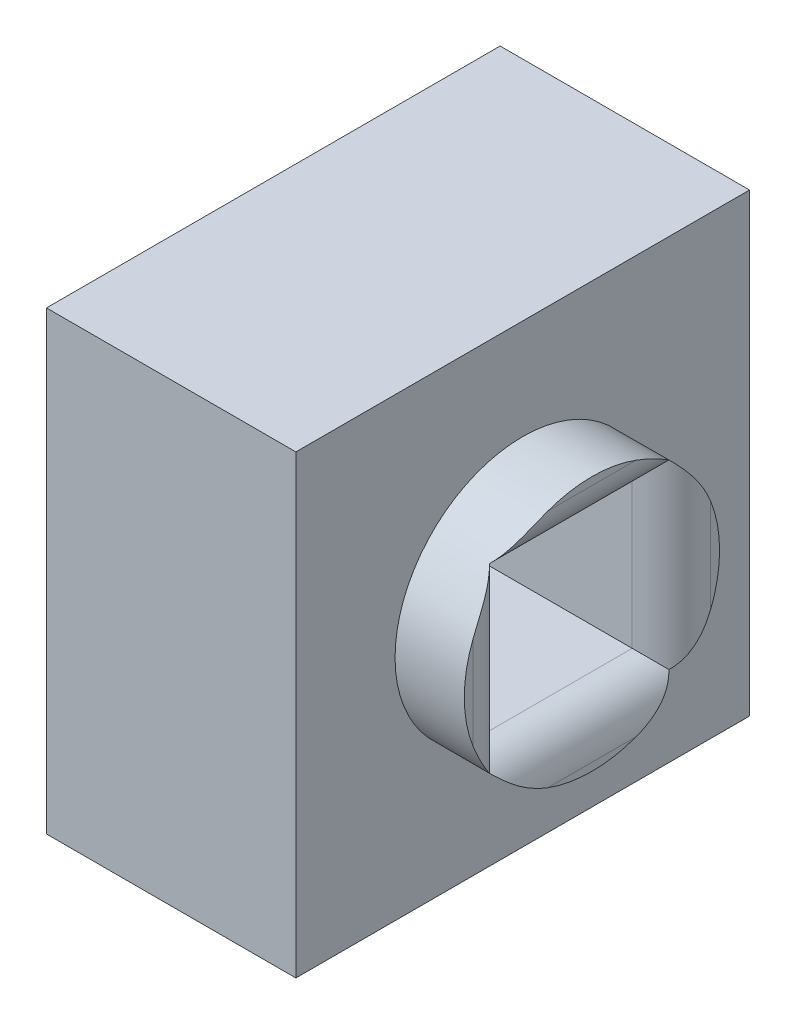
SolidWorks part; units mm, degrees
ref_plane "Front" through (0, 0, 0) normal (0, 0, 1) x (1, 0, 0)
ref_plane "Top" through (0, 0, 0) normal (0, 1, 0) x (1, 0, 0)
ref_plane "Right" through (0, 0, 0) normal (1, 0, 0) x (0, 0, -1)
sketch "Sketch2" plane through (0, 0, 0) normal (1, 0, 0) x (0, 0, -1)
  line L1 (0, 0) -> (8.1, 0)
  line L2 (0, 0) -> (0, 8.2)
  line L3 (0, 8.2) -> (8.1, 8.2)
  line L4 (8.1, 0) -> (8.1, 8.2)
  dimension "D1" = 8.2
  dimension "D2" = 8.1
extrude "Extrude-Thin1" add sketch "Sketch2" along normal blind 12.7 thin thin type one direction wall 7.5
sketch "Sketch3" plane through (12.7, 0, 0) normal (1, 0, 0) x (0, 0, -1)
  line L0 (0, 0) -> (8.1, 8.2) construction
  line L2 (0, 8.2) -> (8.1, 8.2)
  line L3 (0, 8.2) -> (0, 0)
  line L4 (0, 0) -> (8.1, 0)
  line L5 (8.1, 8.2) -> (8.1, 0)
  circle A0 centre (4.05, 4.1) radius 6.5
extrude "Boss-Extrude1" add sketch "Sketch3" along normal blind 3.525
fillet "Fillet1" radius 2 8 edges at (16.225, 4.1, 0) (16.225, 0, -4.05) (16.225, 4.1, -8.1) (16.225, 8.2, -4.05) (0, 8.2, -4.05) (0, 4.1, 0) (0, 0, -4.05) (0, 4.1, -8.1)
